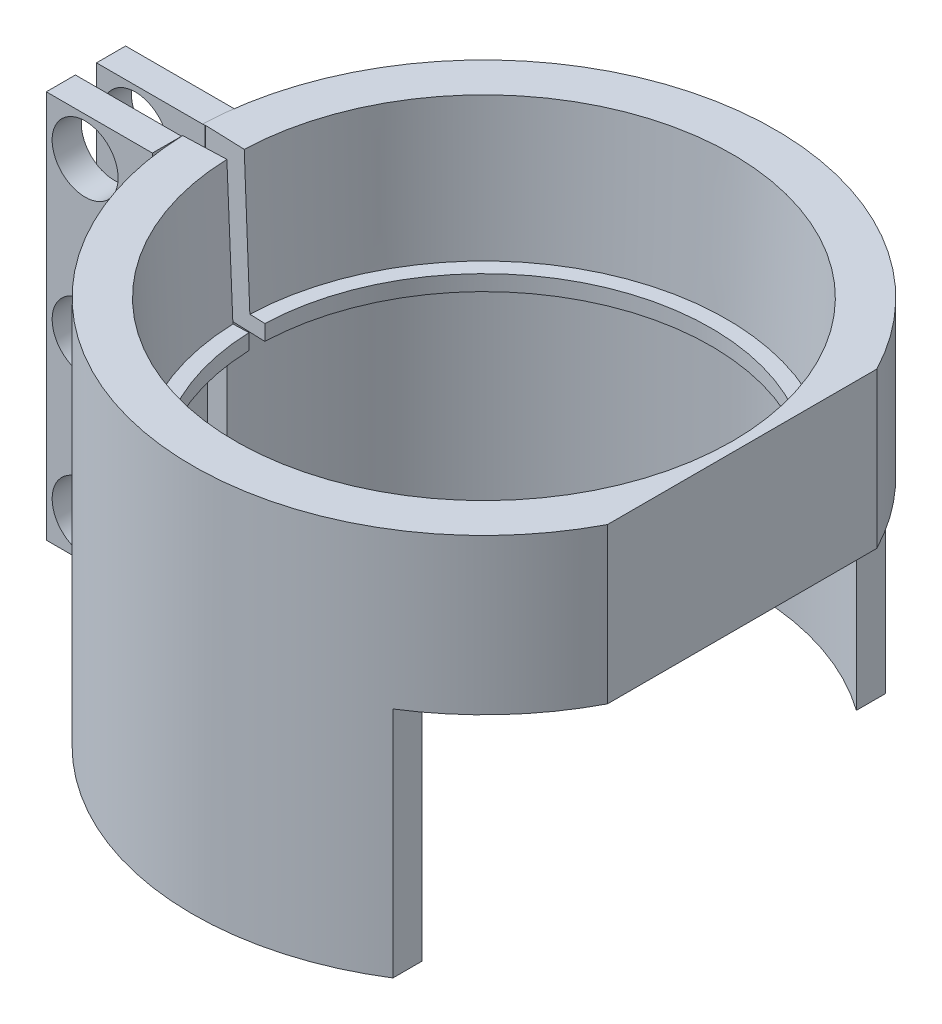
SolidWorks part; units mm, degrees
ref_plane "Front Plane" through (0, 0, 0) normal (0, 0, 1) x (1, 0, 0)
ref_plane "Top Plane" through (0, 0, 0) normal (0, 1, 0) x (1, 0, 0)
ref_plane "Right Plane" through (0, 0, 0) normal (1, 0, 0) x (0, 0, -1)
sketch "Sketch1" plane through (0, 0, 0) normal (0, 1, 0) x (1, 0, 0)
  line L0 (-13.7408, 0.5018) -> (-14.9977, 0.5)
  line L1 (-13.7408, -0.5018) -> (-14.9977, -0.5)
  line L2 (0, 0) -> (7.6847, 0) construction
  line L3 (-14.9977, 0.5) -> (-20.4552, 0.5)
  line L4 (-20.4552, 0.5) -> (-20.4552, 2)
  line L5 (-20.4552, 2) -> (-14.8661, 2)
  line L6 (-14.9977, -0.5) -> (-20.4552, -0.5)
  line L7 (-20.4552, -0.5) -> (-20.4552, -2.0846)
  line L8 (-20.4552, -2.0846) -> (-14.8544, -2.0846)
  arc A0 (-6.875, -11.9078) -> (-6.875, 11.9078) centre (0, 0) ccw
  arc A1 (-7.5, -12.9904) -> (-7.5, 12.9904) centre (0, 0) ccw
  arc A2 (-6.875, 11.9078) -> (-13.7408, 0.5018) centre (0, 0) ccw
  arc A3 (-7.5, 12.9904) -> (-14.8661, 2) centre (0, 0) ccw
  arc A4 (-14.8544, -2.0846) -> (-7.5, -12.9904) centre (0, 0) ccw
  arc A5 (-13.7408, -0.5018) -> (-6.875, -11.9078) centre (0, 0) ccw
  dimension "D1" = 27.5
  dimension "D2" = 1.5
  dimension "D4" = 15
  dimension "D3" = 0.5
  dimension "D6" = 0.5
extrude "Boss-Extrude1" add sketch "Sketch1" along normal blind 12
sketch "Sketch3" plane through (0, 0, 0) normal (1, 0, 0) x (0, 0, -1)
  line L0 (0, 12) -> (-12.2, 12) construction
  line L1 (15, 12) -> (-15, 12) construction
  line L2 (-15, 12) -> (-15, 20)
  line L3 (-15, 20) -> (-12.8, 20)
  line L4 (-12.8, 20) -> (-12.5, 12.8)
  line L5 (-15, 12) -> (-12.2, 12)
  line L6 (0, 12) -> (0, 22.5005) construction
  line L7 (-12.2, 12) -> (-11.7, 12)
  line L8 (-11.7, 12) -> (-11.7, 12.8)
  line L9 (-11.7, 12.8) -> (-12.5, 12.8)
  dimension "D1" = 12.2
  dimension "D2" = 8
  dimension "D3" = 12.8
  dimension "D4" = 0.5
  dimension "D5" = 0.8
  dimension "D6" = 12.5
revolve "Revolve1" add sketch "Sketch3" angle 268 about L6 other way angle 88
sketch "Sketch4" plane through (0, 0, -2) normal (0, 0, -1) x (-1, 0, 0)
  line L0 (14.8661, 12) -> (20.4552, 12) construction
  line L2 (20.4552, 12) -> (20.4552, 0) construction
  line L3 (14.8661, 0) -> (20.4552, 0) construction
  circle A0 centre (18.4552, 10) radius 1.7
  circle A1 centre (18.4552, 2) radius 1.7
  dimension "D1" = 3.4
  dimension "D4" = 3.4
  dimension "D2" = 2
  dimension "D3" = 2
  dimension "D5" = 2
extrude "Cut-Extrude1" cut sketch "Sketch4" against normal through all both and the other way through all
sketch "Sketch5" plane through (0, 0, 2.0846) normal (0, 0, 1) x (1, 0, 0)
  line L0 (-20.4552, 12) -> (-20.4552, 20)
  line L1 (-20.4552, 20) -> (-14.9909, 20)
  line L2 (-14.9909, 20) -> (-14.9909, 12)
  line L3 (-14.9909, 12) -> (-20.4552, 12)
  circle A0 centre (-18.4552, 18) radius 1.7
  dimension "D1" = 3.4
  dimension "D2" = 2
  dimension "D3" = 2
extrude "Boss-Extrude3" add sketch "Sketch5" against normal blind 1.5
sketch "Sketch6" plane through (0, 0, -2) normal (0, 0, -1) x (-1, 0, 0)
  line L1 (14.8661, 12) -> (20.4552, 12)
  line L2 (14.8661, 12) -> (14.8661, 20)
  line L3 (14.8661, 20) -> (20.4552, 20)
  line L4 (20.4552, 12) -> (20.4552, 20)
  circle A0 centre (18.4552, 18) radius 1.7 construction
  circle A1 centre (18.4552, 18) radius 1.7
extrude "Boss-Extrude6" add sketch "Sketch6" against normal blind 1.5 separate body
sketch "Sketch7" plane through (0, 0, 0) normal (0, -1, 0) x (1, 0, 0)
  line L0 (7.9999, 12.6886) -> (7.9999, -14.3125) construction
  line L2 (7.9999, 12.6886) -> (21.3952, 12.6886)
  line L3 (7.9999, 12.6886) -> (7.9999, -14.3125)
  line L4 (7.9999, -14.3125) -> (21.3952, -14.3125)
  line L5 (21.3952, 12.6886) -> (21.3952, -14.3125)
  arc A0 (-14.8661, -2) -> (-14.8544, 2.0846) centre (0, 0) ccw construction
  point P5 (14.9999, -0.0427)
  dimension "D1" = 7
extrude "Cut-Extrude2" cut sketch "Sketch7" against normal up to surface (12 mm away) up to face at (-4.779, 12, 0)
sketch "Sketch8" plane through (0, 20, 0) normal (0, 1, 0) x (1, 0, 0)
  line L1 (13.3, 14.2885) -> (20.2977, 14.2885)
  line L2 (13.3, 14.2885) -> (13.3, -13.1157)
  line L3 (13.3, -13.1157) -> (20.2977, -13.1157)
  line L4 (20.2977, 14.2885) -> (20.2977, -13.1157)
  arc A0 (-12.7922, -0.4467) -> (-12.7922, 0.4467) centre (0, 0) ccw construction
  dimension "D1" = 13.3
extrude "Cut-Extrude3" cut sketch "Sketch8" against normal blind 10
